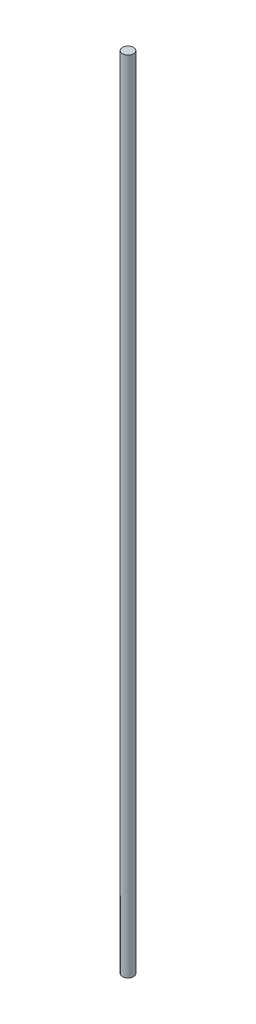
SolidWorks part; units mm, degrees
ref_plane "Front Plane" through (0, 0, 0) normal (0, 0, 1) x (1, 0, 0)
ref_plane "Top Plane" through (0, 0, 0) normal (0, 1, 0) x (1, 0, 0)
ref_plane "Right Plane" through (0, 0, 0) normal (1, 0, 0) x (0, 0, -1)
sketch "Sketch1" plane through (0, 0, 0) normal (0, 1, 0) x (1, 0, 0)
  circle A0 centre (0, 0) radius 6.35
  dimension "D1" = 12.7
extrude "Boss-Extrude1" add sketch "Sketch1" along normal blind 457.2 and the other way blind 457.2
